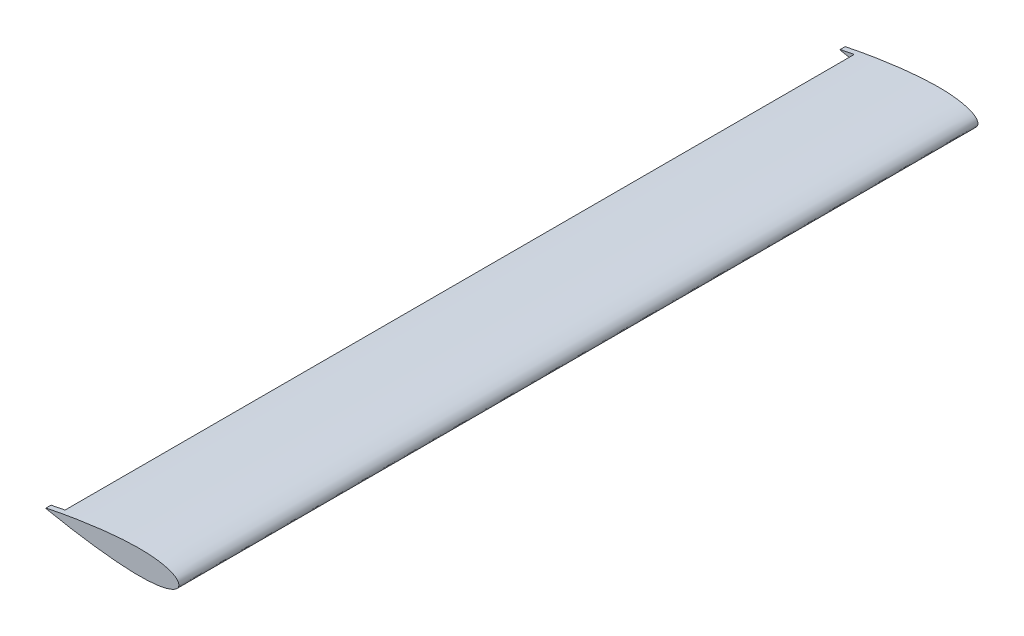
SolidWorks part; units mm, degrees
ref_plane "Alzado" through (0, 0, 0) normal (0, 0, 1) x (1, 0, 0)
ref_plane "Planta" through (0, 0, 0) normal (0, 1, 0) x (1, 0, 0)
ref_plane "Vista lateral" through (0, 0, 0) normal (1, 0, 0) x (0, 0, -1)
sketch "Croquis1" plane through (0, 0, 0) normal (0, 0, 1) x (1, 0, 0)
  line L0 (0, 0) -> (0, -23.5) construction
  line L1 (0, 0) -> (-16, 0) construction
  line L2 (-14.2698, -25.6618) -> (-26, -25.6618)
  line L3 (-26, -25.6618) -> (-26, -33.5)
  line L4 (-26, -33.5) -> (16, -33.5)
  line L5 (16, -33.5) -> (16, 3.8445)
  line L6 (16, 3.8445) -> (-14.2698, 3.8445)
  line L8 (-14.2698, -6.2762) -> (-14.2698, -25.6618)
  line L9 (-14.2698, 3.8445) -> (-26, 3.8445)
  line L10 (-26, 3.8445) -> (-26, -6.2762)
  line L11 (-26, -6.2762) -> (-14.2698, -6.2762)
  circle A0 centre (0, 0) radius 1.5
  dimension "D1" = 3
  dimension "D4" = 16
  dimension "D2" = 23.5
  dimension "D3" = 16
  dimension "D5" = 10
  dimension "D6" = 42
curve "Curva2"
  spline degree 3 poles (266, 0.503, 0) (261.5688, 1.4191, 0) (252.7164, 3.2493, 0) (234.9955, 6.6448, 0) (212.8433, 10.5485, 0) (186.2398, 14.7043, 0) (159.6407, 18.3128, 0) (133.0409, 21.2624, 0) (106.4348, 23.353, 0) (84.237, 24.0962, 0) (66.4893, 23.7999, 0) (53.1677, 23.0109, 0) (39.8211, 21.4881, 0) (28.7128, 19.3599, 0) (19.853, 16.8285, 0) (13.0874, 14.2708, 0) (7.4196, 11.1923, 0) (2.2073, 6.9321, 0) (-1.4404, 0, 0) (2.2073, -6.9321, 0) (7.4196, -11.1923, 0) (13.0874, -14.2708, 0) (19.853, -16.8285, 0) (28.7128, -19.3599, 0) (39.8211, -21.4881, 0) (53.1677, -23.0109, 0) (66.4893, -23.7999, 0) (84.237, -24.0962, 0) (106.4348, -23.353, 0) (133.0409, -21.2624, 0) (159.6407, -18.3128, 0) (186.2398, -14.7043, 0) (212.8433, -10.5485, 0) (234.9955, -6.6448, 0) (252.7164, -3.2493, 0) (261.5688, -1.4191, 0) (266, -0.503, 0) knots 0 0 0 0 0.024604 0.049152 0.098109 0.146905 0.195555 0.244056 0.292409 0.340644 0.364754 0.388905 0.413178 0.437756 0.450305 0.46323 0.477067 0.485036 0.5 0.514964 0.522933 0.53677 0.549695 0.562244 0.586822 0.611095 0.635246 0.659356 0.707591 0.755944 0.804445 0.853095 0.901891 0.950848 0.975396 1 1 1 1
sketch "Croquis6" plane through (0, 0, 0) normal (0, 0, 1) x (1, 0, 0)
  line L2 (-268.433, 0) -> (0, 0) construction
  line L4 (-266, 0.503) -> (-268.433, 0)
  line L5 (-266, -0.503) -> (-268.433, 0)
  spline S2 degree 3 poles (-266, 0.503) (-261.5688, 1.4191) (-252.7164, 3.2493) (-234.9955, 6.6448) (-212.8433, 10.5485) (-186.2398, 14.7043) (-159.6407, 18.3128) (-133.0409, 21.2624) (-106.4348, 23.353) (-84.237, 24.0962) (-66.4893, 23.7999) (-53.1677, 23.0109) (-39.8211, 21.4881) (-28.7128, 19.3599) (-19.853, 16.8285) (-13.0874, 14.2708) (-7.4196, 11.1923) (-2.2073, 6.9321) (1.4404, 0) (-2.2073, -6.9321) (-7.4196, -11.1923) (-13.0874, -14.2708) (-19.853, -16.8285) (-28.7128, -19.3599) (-39.8211, -21.4881) (-53.1677, -23.0109) (-66.4893, -23.7999) (-84.237, -24.0962) (-106.4348, -23.353) (-133.0409, -21.2624) (-159.6407, -18.3128) (-186.2398, -14.7043) (-212.8433, -10.5485) (-234.9955, -6.6448) (-252.7164, -3.2493) (-261.5688, -1.4191) (-266, -0.503) knots 0 0 0 0 0.024604 0.049152 0.098109 0.146905 0.195555 0.244056 0.292409 0.340644 0.364754 0.388905 0.413178 0.437756 0.450305 0.46323 0.477067 0.485036 0.5 0.514964 0.522933 0.53677 0.549695 0.562244 0.586822 0.611095 0.635246 0.659356 0.707591 0.755944 0.804445 0.853095 0.901891 0.950848 0.975396 1 1 1 1
  point P8 (0, 0)
  dimension "D1" = 268.433
sketch "Croquis7" plane through (0, 0, 0) normal (0, 0, 1) x (1, 0, 0)
  line L0 (-266, 0.503) -> (-268.433, 0) construction
  line L1 (-266, 0.503) -> (-268.433, 0) construction
  line L2 (-266, -0.503) -> (-268.433, 0) construction
  line L3 (-266, -0.503) -> (-268.433, 0) construction
  line L4 (-266, -0.503) -> (-266, 0.503)
  spline S0 degree 3 poles (-1155.1432, 1765.3014) (-594.7387, -117.8294) (-424.6464, -29.6947) (-234.9955, 6.6448) (-212.8433, 10.5485) (-186.2398, 14.7043) (-159.6407, 18.3128) (-133.0409, 21.2624) (-106.4348, 23.353) (-84.237, 24.0962) (-66.4893, 23.7999) (-53.1677, 23.0109) (-39.8211, 21.4881) (-28.7128, 19.3599) (-19.853, 16.8285) (-13.0874, 14.2708) (-7.4196, 11.1923) (-2.2073, 6.9321) (1.4404, 0) (-2.2073, -6.9321) (-7.4196, -11.1923) (-13.0874, -14.2708) (-19.853, -16.8285) (-28.7128, -19.3599) (-39.8211, -21.4881) (-53.1677, -23.0109) (-66.4893, -23.7999) (-84.237, -24.0962) (-106.4348, -23.353) (-133.0409, -21.2624) (-159.6407, -18.3128) (-186.2398, -14.7043) (-212.8433, -10.5485) (-234.9955, -6.6448) (-424.6458, 29.6946) (-594.7376, 117.8288) (-1155.1376, -1765.2827) knots -0.951855 -0.951855 -0.951855 -0.951855 0.024604 0.049152 0.098109 0.146905 0.195555 0.244056 0.292409 0.340644 0.364754 0.388905 0.413178 0.437756 0.450305 0.46323 0.477067 0.485036 0.5 0.514964 0.522933 0.53677 0.549695 0.562244 0.586822 0.611095 0.635246 0.659356 0.707591 0.755944 0.804445 0.853095 0.901891 0.950848 0.975396 1.951852 1.951852 1.951852 1.951852 only from (-266, 0.503) to (-266, -0.503) construction
  spline S1 degree 3 poles (-266, 0.503) (-261.5688, 1.4191) (-252.7164, 3.2493) (-234.9955, 6.6448) (-212.8433, 10.5485) (-186.2398, 14.7043) (-159.6407, 18.3128) (-133.0409, 21.2624) (-106.4348, 23.353) (-84.237, 24.0962) (-66.4893, 23.7999) (-53.1677, 23.0109) (-39.8211, 21.4881) (-28.7128, 19.3599) (-19.853, 16.8285) (-13.0874, 14.2708) (-7.4196, 11.1923) (-2.2073, 6.9321) (1.4404, 0) (-2.2073, -6.9321) (-7.4196, -11.1923) (-13.0874, -14.2708) (-19.853, -16.8285) (-28.7128, -19.3599) (-39.8211, -21.4881) (-53.1677, -23.0109) (-66.4893, -23.7999) (-84.237, -24.0962) (-106.4348, -23.353) (-133.0409, -21.2624) (-159.6407, -18.3128) (-186.2398, -14.7043) (-212.8433, -10.5485) (-234.9955, -6.6448) (-252.7164, -3.2493) (-261.5688, -1.4191) (-266, -0.503) knots 0 0 0 0 0.024604 0.049152 0.098109 0.146905 0.195555 0.244056 0.292409 0.340644 0.364754 0.388905 0.413178 0.437756 0.450305 0.46323 0.477067 0.485036 0.5 0.514964 0.522933 0.53677 0.549695 0.562244 0.586822 0.611095 0.635246 0.659356 0.707591 0.755944 0.804445 0.853095 0.901891 0.950848 0.975396 1 1 1 1
extrude "Saliente-Extruir1" add sketch "Croquis7" along normal mid plane 1600
sketch "Croquis8" plane through (0, 0, 0) normal (0, 0, 1) x (1, 0, 0)
  line L0 (-267.9302, -0.83) -> (-267.9302, 0.83)
  line L1 (-237.8077, -6.0739) -> (-237.8077, 6.0739)
  line L2 (-267.9302, -0.83) -> (-267.9302, 0.83) construction
  spline S0 degree 3 poles (-266, 0.503) (-261.5688, 1.4191) (-252.7164, 3.2493) (-234.9955, 6.6448) (-212.8433, 10.5485) (-186.2398, 14.7043) (-159.6407, 18.3128) (-133.0409, 21.2624) (-106.4348, 23.353) (-84.237, 24.0962) (-66.4893, 23.7999) (-53.1677, 23.0109) (-39.8211, 21.4881) (-28.7128, 19.3599) (-19.853, 16.8285) (-13.0874, 14.2708) (-7.4196, 11.1923) (-2.2073, 6.9321) (1.4404, 0) (-2.2073, -6.9321) (-7.4196, -11.1923) (-13.0874, -14.2708) (-19.853, -16.8285) (-28.7128, -19.3599) (-39.8211, -21.4881) (-53.1677, -23.0109) (-66.4893, -23.7999) (-84.237, -24.0962) (-106.4348, -23.353) (-133.0409, -21.2624) (-159.6407, -18.3128) (-186.2398, -14.7043) (-212.8433, -10.5485) (-234.9955, -6.6448) (-252.7164, -3.2493) (-261.5688, -1.4191) (-266, -0.503) knots 0 0 0 0 0.024604 0.049152 0.098109 0.146905 0.195555 0.244056 0.292409 0.340644 0.364754 0.388905 0.413178 0.437756 0.450305 0.46323 0.477067 0.485036 0.5 0.514964 0.522933 0.53677 0.549695 0.562244 0.586822 0.611095 0.635246 0.659356 0.707591 0.755944 0.804445 0.853095 0.901891 0.950848 0.975396 1 1 1 1 construction
  spline S1 degree 3 poles (-267.9302, 0.83) (-257.8902, 2.5829) (-247.8502, 4.3359) (-237.8077, 6.0739) knots 0 0 0 0 0.011104 0.011104 0.011104 0.011104
  spline S2 degree 3 poles (-237.8077, -6.0739) (-247.8502, -4.3359) (-257.8902, -2.5829) (-267.9302, -0.83) knots 0.988896 0.988896 0.988896 0.988896 1 1 1 1
  dimension "D2" = 1.6599
extrude "Cortar-Extruir1" cut sketch "Croquis8" against normal mid plane 1580
